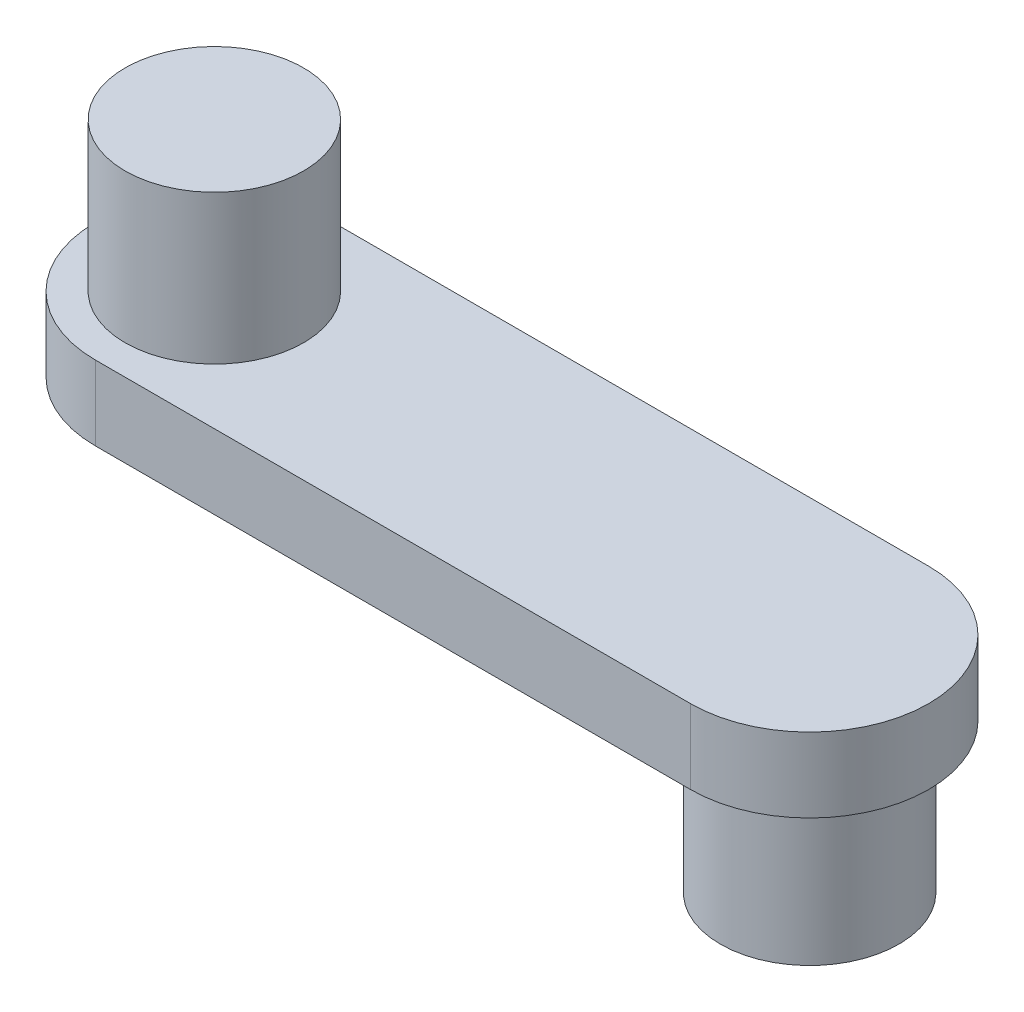
SolidWorks part; units mm, degrees
material "Cast Alloy Steel"
ref_plane "Front Plane" through (0, 0, 0) normal (0, 0, 1) x (1, 0, 0)
ref_plane "Top Plane" through (0, 0, 0) normal (0, 1, 0) x (1, 0, 0)
ref_plane "Right Plane" through (0, 0, 0) normal (1, 0, 0) x (0, 0, -1)
sketch "Sketch1" plane through (0, 0, 0) normal (0, 1, 0) x (1, 0, 0)
  line L0 (0, 0) -> (40, 0) construction
  line L1 (0, 8) -> (40, 8)
  line L2 (0, -8) -> (40, -8)
  arc A0 (0, 8) -> (0, -8) centre (0, 0) ccw
  arc A1 (40, -8) -> (40, 8) centre (40, 0) ccw
  circle A2 centre (0, 0) radius 6
  circle A3 centre (40, 0) radius 6
  point P3 (20, 0)
  dimension "D2" = 8
  dimension "D3" = 12
  dimension "D4" = 12
  dimension "D1" = 40
extrude "Boss-Extrude1" add sketch "Sketch1" along normal blind 5 contours L2 A1 L1 A0 A2 A3 | A2 | A3 region at (20, 0, 0) region at (0, 0, 0) region at (40, 0, 0)
extrude "Boss-Extrude2" add sketch "Sketch1<3>" along normal blind 15 contours A2
sketch "Sketch1<3>" plane through (0, 0, 0) normal (0, 1, 0) x (1, 0, 0) same geometry as "Sketch1"
extrude "Boss-Extrude3" add sketch "Sketch1<4>" against normal blind 10 contours A3
sketch "Sketch1<4>" plane through (0, 0, 0) normal (0, 1, 0) x (1, 0, 0) same geometry as "Sketch1"
